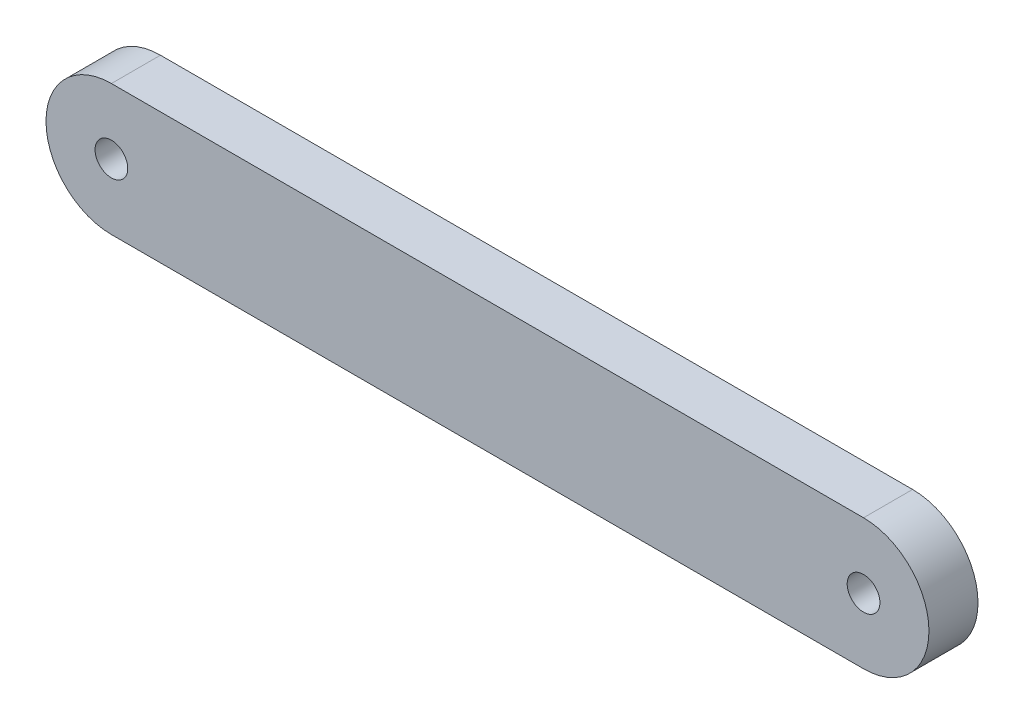
SolidWorks part; units mm, degrees
ref_plane "Plan de face" through (0, 0, 0) normal (0, 0, 1) x (1, 0, 0)
ref_plane "Plan de dessus" through (0, 0, 0) normal (0, 1, 0) x (1, 0, 0)
ref_plane "Plan de droite" through (0, 0, 0) normal (1, 0, 0) x (0, 0, -1)
sketch "Esquisse1" plane through (0, 0, 0) normal (0, 0, 1) x (1, 0, 0)
  line L0 (4, 8) -> (4, 0) construction
  line L1 (0, 0) -> (54, 0) construction
  line L2 (0, 0) -> (0, 8) construction
  line L3 (0, 8) -> (54, 8) construction
  line L4 (54, 0) -> (54, 8) construction
  line L5 (50, 8) -> (50, 0) construction
  line L6 (50, 8) -> (4, 8)
  line L7 (4, 0) -> (50, 0)
  arc A0 (4, 0) -> (4, 8) centre (4, 4) cw
  arc A1 (50, 8) -> (50, 0) centre (50, 4) cw
  circle A2 centre (4, 4) radius 1
  circle A3 centre (50, 4) radius 1
  dimension "D2" = 2
  dimension "D1" = 8
  dimension "D3" = 54
extrude "Boss.-Extru.1" add sketch "Esquisse1" along normal blind 3
